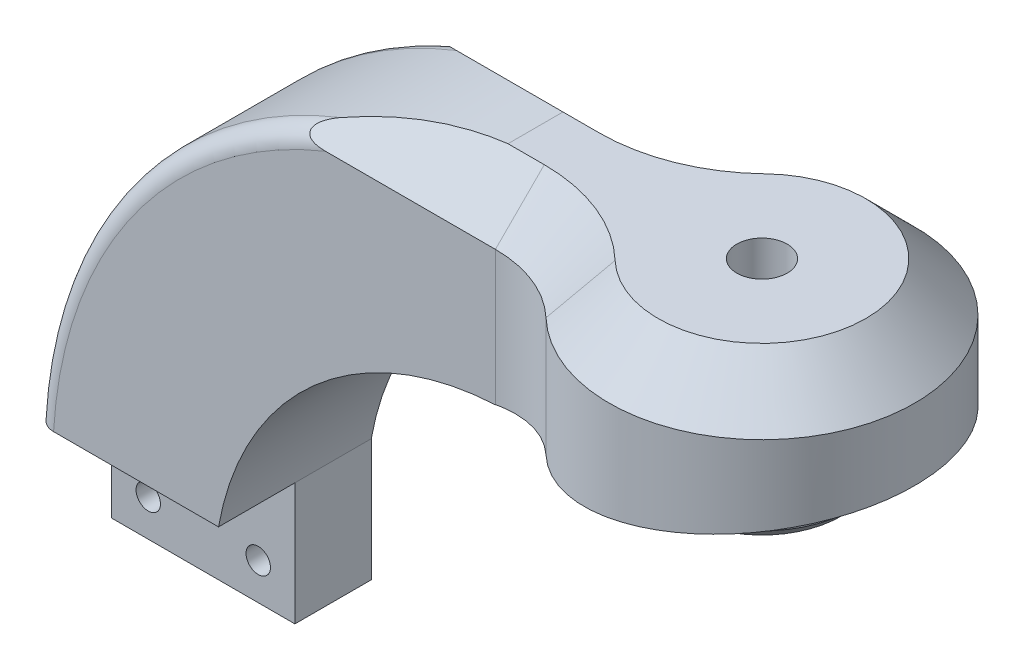
SolidWorks part; units mm, degrees
material "ABS"
ref_plane "Front Plane" through (0, 0, 0) normal (0, 0, 1) x (1, 0, 0)
ref_plane "Top Plane" through (0, 0, 0) normal (0, 1, 0) x (1, 0, 0)
ref_plane "Right Plane" through (0, 0, 0) normal (1, 0, 0) x (0, 0, -1)
sketch "Sketch1" plane through (0, 0, 0) normal (0, 0, 1) x (1, 0, 0)
  line L0 (69.3749, 90) -> (120, 90)
  line L1 (0, 0) -> (30, 0)
  line L2 (0, 0) -> (0, 20)
  line L3 (20, 90) -> (30, 90)
  line L4 (30, 0) -> (30, 20)
  line L5 (20, 90) -> (30, 90)
  line L7 (76.2846, 60) -> (120, 60)
  line L8 (120, 90) -> (120, 60)
  arc A1 (30, 20) -> (79.2135, 60) centre (77.7491, 11.5271) cw
  arc A2 (0, 20) -> (78.8823, 90) centre (74.1286, 15.9111) cw
  dimension "D4" = 20
  dimension "D5" = 20
  dimension "D1" = 30
  dimension "D2" = 30
  dimension "D3" = 90
extrude "Boss-Extrude1" add sketch "Sketch1" along normal blind 25 contours L2 L1 L4 L7 L8 L5 L3 region at (51.6447, 55.6367, 0)
sketch "Sketch3" plane through (0, 90, 0) normal (0, 1, 0) x (1, 0, 0)
  line L0 (120, -12.5) -> (92.8851, -12.5) construction
  line L1 (120, -25) -> (120, 0) construction
  line L2 (69.3749, 0) -> (69.3749, -25)
  line L3 (69.3749, -25) -> (75.3178, -25)
  line L4 (69.3749, -25) -> (120, -25) construction
  line L5 (69.3749, 0) -> (75.3178, 0)
  line L6 (69.3749, 0) -> (120, 0) construction
  arc A0 (89.151, -30.5556) -> (89.151, 5.5556) centre (106.4426, -12.5) ccw
  arc A1 (75.3178, -25) -> (89.151, -30.5556) centre (75.3178, -45) cw
  arc A2 (75.3178, 0) -> (89.151, 5.5556) centre (75.3178, 20) ccw
  point P17 (84.7919, -25)
  point P20 (84.7919, 0)
  dimension "D1" = 50
  dimension "D2" = 20
extrude "Boss-Extrude3" add sketch "Sketch3" against normal up to surface (30 mm away) up to face at (99.6068, 60, 12.5)
ref_axis "Axis1" through (106.4426, 60, 12.5) along (0, 1, 0)
sketch "Sketch4" plane through (0, 0, 0) normal (1, 0, 0) x (0, 0, -1)
  line L0 (-25, 0) -> (0, 0) construction
  line L1 (-12.5, 0) -> (-42.5, 0)
  line L2 (-12.5, 0) -> (-12.5, 20)
  line L3 (-12.5, 20) -> (-42.5, 20)
  line L4 (-42.5, 0) -> (-42.5, 20)
  dimension "D1" = 30
  dimension "D2" = 20
extrude "Cut-Extrude1" cut sketch "Sketch4" along normal blind 49
sketch "Sketch5" plane through (0, 0, 12.5) normal (0, 0, 1) x (1, 0, 0)
  line L0 (30, 14) -> (0, 14) construction
  line L1 (30, 20) -> (30, 0) construction
  line L2 (0, 20) -> (0, 0) construction
  line L3 (30, 20) -> (0, 20) construction
  line L4 (30, 6) -> (0, 6) construction
  line L6 (30, 0) -> (0, 0) construction
  line L7 (0, 0) -> (0, 20) construction
  line L8 (30, 0) -> (30, 20) construction
  circle A0 centre (24, 6) radius 2
  circle A1 centre (6, 6) radius 2
  circle A2 centre (15, 14) radius 2
  dimension "D2" = 4
  dimension "D3" = 4
  dimension "D4" = 4
  dimension "D1" = 6
  dimension "D5" = 15
  dimension "D6" = 6
  dimension "D7" = 6
  dimension "D8" = 6
extrude "Cut-Extrude2" cut sketch "Sketch5" against normal blind 49
sketch "Sketch6" plane through (0, 0, 0) normal (0, 0, 1) x (1, 0, 0)
  line L0 (75.3178, 60) -> (136.8515, 71.3075)
  line L1 (136.8515, 71.3075) -> (136.8515, 40.5377)
  line L2 (136.8515, 40.5377) -> (75.3178, 40.5377)
  line L3 (75.3178, 40.5377) -> (75.3178, 60)
extrude "Cut-Extrude3" cut sketch "Sketch6" against normal mid plane 78
sketch "Sketch7" plane through (0, 90, 0) normal (0, 1, 0) x (1, 0, 0)
  circle A0 centre (106.4426, -12.5) radius 4.125
  dimension "D1" = 8.25
extrude "Cut-Extrude4" cut sketch "Sketch7" against normal blind 78
sketch "Sketch8" plane through (0, 90, 0) normal (0, 1, 0) x (1, 0, 0)
  circle A0 centre (106.4426, -12.5) radius 4.125
  circle A1 centre (106.4426, -12.5) radius 15
  dimension "D1" = 30
extrude "Boss-Extrude4" add sketch "Sketch8" against normal blind 30
sketch "Sketch9" plane through (0, 60, 0) normal (0, -1, 0) x (1, 0, 0)
  line L0 (106.4426, 12.5) -> (126.7329, 12.5) construction
  line L2 (114.5255, 12.5) -> (110.484, 19.5)
  line L3 (110.484, 19.5) -> (102.4011, 19.5)
  line L4 (102.4011, 19.5) -> (98.3596, 12.5)
  line L5 (98.3596, 12.5) -> (102.4011, 5.5)
  line L6 (102.4011, 5.5) -> (110.484, 5.5)
  line L7 (110.484, 5.5) -> (114.5255, 12.5)
  circle A0 centre (106.4426, 12.5) radius 7 construction
  dimension "D1" = 14
extrude "Cut-Extrude5" cut sketch "Sketch9" against normal blind 7
chamfer "Chamfer1" distance 8 angle 45 5 edges at (72.3464, 90, 25) (72.3464, 90, 0) (82.7714, 90, 26.4408) (82.7714, 90, -1.4408) (131.4426, 90, 12.5)
fillet "Fillet1" radius 3 2 edges at (11.8839, 56.3754, 0) (11.8839, 56.3754, 25)
chamfer "Chamfer2" distance 2 angle 45 1 edges at (106.4426, 60, 27.5)
